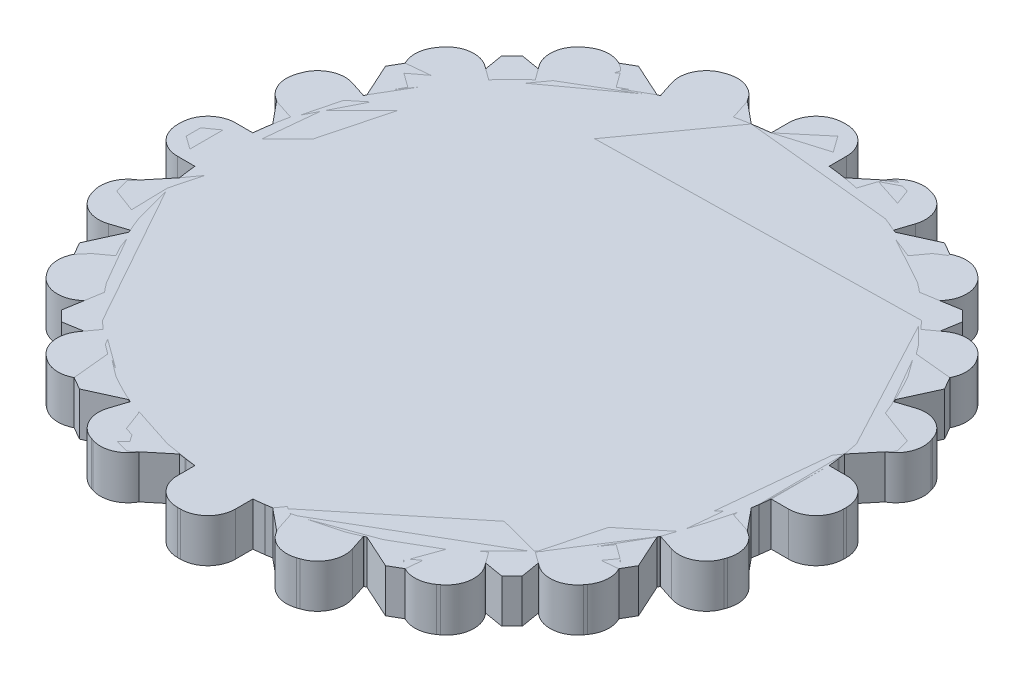
SolidWorks part; units mm, degrees
ref_plane "Front Plane" through (0, 0, 0) normal (0, 0, 1) x (1, 0, 0)
ref_plane "Top Plane" through (0, 0, 0) normal (0, 1, 0) x (1, 0, 0)
ref_plane "Right Plane" through (0, 0, 0) normal (1, 0, 0) x (0, 0, -1)
sketch "Sketch1" plane through (0, 0, 0) normal (0, 1, 0) x (1, 0, 0)
  line L86 (-3.1424, 4.8669) -> (1.8576, 4.8669)
  line L87 (-3.1424, 4.8669) -> (-3.1424, 1.8669)
  line L111 (-1.1424, 15.3669) -> (-0.1424, 15.3669)
  line L112 (-0.1424, 15.3669) -> (1.3576, 13.1649)
  line L113 (-1.1424, 15.3669) -> (-2.6424, 13.1649)
  line L114 (5.7906, 13.5092) -> (5.9886, 10.8522)
  line L115 (4.9246, 14.0092) -> (5.7906, 13.5092)
  line L116 (4.9246, 14.0092) -> (2.5245, 12.8522)
  line L117 (9.9999, 8.9339) -> (8.8429, 6.5338)
  line L118 (9.4999, 9.7999) -> (9.9999, 8.9339)
  line L119 (9.4999, 9.7999) -> (6.8429, 9.9979)
  line L120 (11.3576, 2.8669) -> (9.1556, 1.3669)
  line L121 (11.3576, 3.8669) -> (11.3576, 2.8669)
  line L122 (11.3576, 3.8669) -> (9.1556, 5.3669)
  line L123 (9.4999, -3.0661) -> (6.8429, -3.2641)
  line L124 (9.9999, -2.2001) -> (9.4999, -3.0661)
  line L125 (9.9999, -2.2001) -> (8.8429, 0.2)
  line L126 (4.9246, -7.2754) -> (2.5245, -6.1184)
  line L127 (5.7906, -6.7754) -> (4.9246, -7.2754)
  line L128 (5.7906, -6.7754) -> (5.9886, -4.1184)
  line L129 (-1.1424, -8.6331) -> (-2.6424, -6.4311)
  line L130 (-0.1424, -8.6331) -> (-1.1424, -8.6331)
  line L131 (-0.1424, -8.6331) -> (1.3576, -6.4311)
  line L132 (-7.0754, -6.7754) -> (-7.2734, -4.1184)
  line L133 (-6.2094, -7.2754) -> (-7.0754, -6.7754)
  line L134 (-6.2094, -7.2754) -> (-3.8093, -6.1184)
  line L135 (-11.2847, -2.2001) -> (-10.1277, 0.2)
  line L136 (-10.7847, -3.0661) -> (-11.2847, -2.2001)
  line L137 (-10.7847, -3.0661) -> (-8.1277, -3.2641)
  line L138 (-12.6424, 3.8669) -> (-10.4404, 5.3669)
  line L139 (-12.6424, 2.8669) -> (-12.6424, 3.8669)
  line L140 (-12.6424, 2.8669) -> (-10.4404, 1.3669)
  line L141 (-10.7847, 9.7999) -> (-8.1277, 9.9979)
  line L142 (-11.2847, 8.9339) -> (-10.7847, 9.7999)
  line L143 (-11.2847, 8.9339) -> (-10.1277, 6.5338)
  line L144 (-6.2094, 14.0092) -> (-3.8093, 12.8522)
  line L145 (-7.0754, 13.5092) -> (-6.2094, 14.0092)
  line L146 (-7.0754, 13.5092) -> (-7.2734, 10.8522)
  line L147 (-3.1424, 1.8669) -> (1.8576, 1.8669)
  line L148 (1.8576, 4.8669) -> (1.8576, 1.8669)
  line L149 (-3.1424, 4.8669) -> (1.8576, 1.8669) construction
  line L150 (-3.1424, 1.8669) -> (1.8576, 4.8669) construction
  arc A43 (-2.6424, 13.1649) -> (-3.8093, 12.8522) centre (-0.6424, 3.3669) ccw
  arc A44 (-7.2734, 10.8522) -> (-8.1277, 9.9979) centre (-0.6424, 3.3669) ccw
  arc A45 (-10.1277, 6.5338) -> (-10.4404, 5.3669) centre (-0.6424, 3.3669) ccw
  arc A46 (-10.4404, 1.3669) -> (-10.1277, 0.2) centre (-0.6424, 3.3669) ccw
  arc A47 (-8.1277, -3.2641) -> (-7.2734, -4.1184) centre (-0.6424, 3.3669) ccw
  arc A48 (-3.8093, -6.1184) -> (-2.6424, -6.4311) centre (-0.6424, 3.3669) ccw
  arc A49 (1.3576, -6.4311) -> (2.5245, -6.1184) centre (-0.6424, 3.3669) ccw
  arc A50 (5.9886, -4.1184) -> (6.8429, -3.2641) centre (-0.6424, 3.3669) ccw
  arc A51 (8.8429, 0.2) -> (9.1556, 1.3669) centre (-0.6424, 3.3669) ccw
  arc A52 (9.1556, 5.3669) -> (8.8429, 6.5338) centre (-0.6424, 3.3669) ccw
  arc A53 (6.8429, 9.9979) -> (5.9886, 10.8522) centre (-0.6424, 3.3669) ccw
  arc A54 (2.5245, 12.8522) -> (1.3576, 13.1649) centre (-0.6424, 3.3669) ccw
  point P6 (0, 0)
  point P8 (0, 0)
  point P9 (0, 0)
  point P12 (0, 2.7462)
  point P17 (0, 0)
  point P18 (0, 2.7462)
  point P22 (-2.5, 0.7462)
  point P63 (0, 0)
  point P68 (0, 0)
  point P69 (-0.6424, 3.3669)
  point P119 (0, 0)
  dimension "D1" = 20
  dimension "D2" = 3
  dimension "D3" = 5
  dimension "D8" = 12
sketch "Sketch2" plane through (0, 0, 0) normal (0, 1, 0) x (1, 0, 0)
  line L0 (-2, 0) -> (2, 0)
  line L1 (-23, -0.1) -> (-23, 0.1)
  line L2 (-21.1, 2) -> (-19.8997, 2)
  line L3 (-21.1, -2) -> (-19.8997, -2)
  line L4 (-20.6853, 4.6181) -> (-19.5438, 4.2472)
  line L5 (-19.4493, 8.4224) -> (-18.3078, 8.0515)
  line L6 (-21.9052, 7.0123) -> (-21.8434, 7.2025)
  line L7 (-18.2458, 10.7842) -> (-17.2748, 10.0787)
  line L8 (-15.8947, 14.0203) -> (-14.9237, 13.3148)
  line L9 (-18.6662, 13.4382) -> (-18.5486, 13.6)
  line L10 (-14.0203, 15.8947) -> (-13.3148, 14.9237)
  line L11 (-10.7842, 18.2458) -> (-10.0787, 17.2748)
  line L12 (-13.6, 18.5486) -> (-13.4382, 18.6662)
  line L13 (-8.4224, 19.4493) -> (-8.0515, 18.3078)
  line L14 (-4.6181, 20.6853) -> (-4.2472, 19.5438)
  line L15 (-7.2025, 21.8434) -> (-7.0123, 21.9052)
  line L16 (-2, 21.1) -> (-2, 19.8997)
  line L17 (2, 21.1) -> (2, 19.8997)
  line L18 (-0.1, 23) -> (0.1, 23)
  line L19 (4.6181, 20.6853) -> (4.2472, 19.5438)
  line L20 (8.4224, 19.4493) -> (8.0515, 18.3078)
  line L21 (7.0123, 21.9052) -> (7.2025, 21.8434)
  line L22 (10.7842, 18.2458) -> (10.0787, 17.2748)
  line L23 (14.0203, 15.8947) -> (13.3148, 14.9237)
  line L24 (13.4382, 18.6662) -> (13.6, 18.5486)
  line L25 (15.8947, 14.0203) -> (14.9237, 13.3148)
  line L26 (18.2458, 10.7842) -> (17.2748, 10.0787)
  line L27 (18.5486, 13.6) -> (18.6662, 13.4382)
  line L28 (19.4493, 8.4224) -> (18.3078, 8.0515)
  line L29 (20.6853, 4.6181) -> (19.5438, 4.2472)
  line L30 (21.8434, 7.2025) -> (21.9052, 7.0123)
  line L31 (21.1, 2) -> (19.8997, 2)
  line L32 (21.1, -2) -> (19.8997, -2)
  line L33 (23, 0.1) -> (23, -0.1)
  line L34 (20.6853, -4.6181) -> (19.5438, -4.2472)
  line L35 (19.4493, -8.4224) -> (18.3078, -8.0515)
  line L36 (21.9052, -7.0123) -> (21.8434, -7.2025)
  line L37 (18.2458, -10.7842) -> (17.2748, -10.0787)
  line L38 (15.8947, -14.0203) -> (14.9237, -13.3148)
  line L39 (18.6662, -13.4382) -> (18.5486, -13.6)
  line L40 (14.0203, -15.8947) -> (13.3148, -14.9237)
  line L41 (10.7842, -18.2458) -> (10.0787, -17.2748)
  line L42 (13.6, -18.5486) -> (13.4382, -18.6662)
  line L43 (8.4224, -19.4493) -> (8.0515, -18.3078)
  line L44 (4.6181, -20.6853) -> (4.2472, -19.5438)
  line L45 (7.2025, -21.8434) -> (7.0123, -21.9052)
  line L46 (2, -21.1) -> (2, -19.8997)
  line L47 (-2, -21.1) -> (-2, -19.8997)
  line L48 (0.1, -23) -> (-0.1, -23)
  line L49 (-4.6181, -20.6853) -> (-4.2472, -19.5438)
  line L50 (-8.4224, -19.4493) -> (-8.0515, -18.3078)
  line L51 (-7.0123, -21.9052) -> (-7.2025, -21.8434)
  line L52 (-10.7842, -18.2458) -> (-10.0787, -17.2748)
  line L53 (-14.0203, -15.8947) -> (-13.3148, -14.9237)
  line L54 (-13.4382, -18.6662) -> (-13.6, -18.5486)
  line L55 (-15.8947, -14.0203) -> (-14.9237, -13.3148)
  line L56 (-18.2458, -10.7842) -> (-17.2748, -10.0787)
  line L57 (-18.5486, -13.6) -> (-18.6662, -13.4382)
  line L58 (-19.4493, -8.4224) -> (-18.3078, -8.0515)
  line L59 (-20.6853, -4.6181) -> (-19.5438, -4.2472)
  line L60 (-21.8434, -7.2025) -> (-21.9052, -7.0123)
  arc A0 (-18.3078, -8.0515) -> (-17.2748, -10.0787) centre (0, 0) ccw
  arc A1 (-21.1, 2) -> (-23, 0.1) centre (-21.1, 0.1) ccw
  arc A2 (-21.1, -2) -> (-23, -0.1) centre (-21.1, -0.1) cw
  arc A3 (-20.6853, 4.6181) -> (-21.9052, 7.0123) centre (-20.0982, 6.4252) cw
  arc A4 (-19.4493, 8.4224) -> (-21.8434, 7.2025) centre (-20.0364, 6.6154) ccw
  arc A5 (-18.2458, 10.7842) -> (-18.6662, 13.4382) centre (-17.129, 12.3214) cw
  arc A6 (-15.8947, 14.0203) -> (-18.5486, 13.6) centre (-17.0115, 12.4832) ccw
  arc A7 (-14.0203, 15.8947) -> (-13.6, 18.5486) centre (-12.4832, 17.0115) cw
  arc A8 (-10.7842, 18.2458) -> (-13.4382, 18.6662) centre (-12.3214, 17.129) ccw
  arc A9 (-8.4224, 19.4493) -> (-7.2025, 21.8434) centre (-6.6154, 20.0364) cw
  arc A10 (-4.6181, 20.6853) -> (-7.0123, 21.9052) centre (-6.4252, 20.0982) ccw
  arc A11 (-2, 21.1) -> (-0.1, 23) centre (-0.1, 21.1) cw
  arc A12 (2, 21.1) -> (0.1, 23) centre (0.1, 21.1) ccw
  arc A13 (4.6181, 20.6853) -> (7.0123, 21.9052) centre (6.4252, 20.0982) cw
  arc A14 (8.4224, 19.4493) -> (7.2025, 21.8434) centre (6.6154, 20.0364) ccw
  arc A15 (10.7842, 18.2458) -> (13.4382, 18.6662) centre (12.3214, 17.129) cw
  arc A16 (14.0203, 15.8947) -> (13.6, 18.5486) centre (12.4832, 17.0115) ccw
  arc A17 (15.8947, 14.0203) -> (18.5486, 13.6) centre (17.0115, 12.4832) cw
  arc A18 (18.2458, 10.7842) -> (18.6662, 13.4382) centre (17.129, 12.3214) ccw
  arc A19 (19.4493, 8.4224) -> (21.8434, 7.2025) centre (20.0364, 6.6154) cw
  arc A20 (20.6853, 4.6181) -> (21.9052, 7.0123) centre (20.0982, 6.4252) ccw
  arc A21 (21.1, 2) -> (23, 0.1) centre (21.1, 0.1) cw
  arc A22 (21.1, -2) -> (23, -0.1) centre (21.1, -0.1) ccw
  arc A23 (20.6853, -4.6181) -> (21.9052, -7.0123) centre (20.0982, -6.4252) cw
  arc A24 (19.4493, -8.4224) -> (21.8434, -7.2025) centre (20.0364, -6.6154) ccw
  arc A25 (18.2458, -10.7842) -> (18.6662, -13.4382) centre (17.129, -12.3214) cw
  arc A26 (15.8947, -14.0203) -> (18.5486, -13.6) centre (17.0115, -12.4832) ccw
  arc A27 (14.0203, -15.8947) -> (13.6, -18.5486) centre (12.4832, -17.0115) cw
  arc A28 (10.7842, -18.2458) -> (13.4382, -18.6662) centre (12.3214, -17.129) ccw
  arc A29 (8.4224, -19.4493) -> (7.2025, -21.8434) centre (6.6154, -20.0364) cw
  arc A30 (4.6181, -20.6853) -> (7.0123, -21.9052) centre (6.4252, -20.0982) ccw
  arc A31 (2, -21.1) -> (0.1, -23) centre (0.1, -21.1) cw
  arc A32 (-2, -21.1) -> (-0.1, -23) centre (-0.1, -21.1) ccw
  arc A33 (-4.6181, -20.6853) -> (-7.0123, -21.9052) centre (-6.4252, -20.0982) cw
  arc A34 (-8.4224, -19.4493) -> (-7.2025, -21.8434) centre (-6.6154, -20.0364) ccw
  arc A35 (-10.7842, -18.2458) -> (-13.4382, -18.6662) centre (-12.3214, -17.129) cw
  arc A36 (-14.0203, -15.8947) -> (-13.6, -18.5486) centre (-12.4832, -17.0115) ccw
  arc A37 (-15.8947, -14.0203) -> (-18.5486, -13.6) centre (-17.0115, -12.4832) cw
  arc A38 (-18.2458, -10.7842) -> (-18.6662, -13.4382) centre (-17.129, -12.3214) ccw
  arc A39 (-19.4493, -8.4224) -> (-21.8434, -7.2025) centre (-20.0364, -6.6154) cw
  arc A40 (-20.6853, -4.6181) -> (-21.9052, -7.0123) centre (-20.0982, -6.4252) ccw
  arc A41 (-19.8997, -2) -> (-19.5438, -4.2472) centre (0, 0) ccw
  arc A42 (-19.5438, 4.2472) -> (-19.8997, 2) centre (0, 0) ccw
  arc A43 (-17.2748, 10.0787) -> (-18.3078, 8.0515) centre (0, 0) ccw
  arc A44 (-13.3148, 14.9237) -> (-14.9237, 13.3148) centre (0, 0) ccw
  arc A45 (-8.0515, 18.3078) -> (-10.0787, 17.2748) centre (0, 0) ccw
  arc A46 (-2, 19.8997) -> (-4.2472, 19.5438) centre (0, 0) ccw
  arc A47 (4.2472, 19.5438) -> (2, 19.8997) centre (0, 0) ccw
  arc A48 (10.0787, 17.2748) -> (8.0515, 18.3078) centre (0, 0) ccw
  arc A49 (14.9237, 13.3148) -> (13.3148, 14.9237) centre (0, 0) ccw
  arc A50 (18.3078, 8.0515) -> (17.2748, 10.0787) centre (0, 0) ccw
  arc A51 (19.8997, 2) -> (19.5438, 4.2472) centre (0, 0) ccw
  arc A52 (19.5438, -4.2472) -> (19.8997, -2) centre (0, 0) ccw
  arc A53 (17.2748, -10.0787) -> (18.3078, -8.0515) centre (0, 0) ccw
  arc A54 (13.3148, -14.9237) -> (14.9237, -13.3148) centre (0, 0) ccw
  arc A55 (8.0515, -18.3078) -> (10.0787, -17.2748) centre (0, 0) ccw
  arc A56 (2, -19.8997) -> (4.2472, -19.5438) centre (0, 0) ccw
  arc A57 (-10.0787, -17.2748) -> (-8.0515, -18.3078) centre (0, 0) ccw
  arc A58 (-4.2472, -19.5438) -> (-2, -19.8997) centre (0, 0) ccw
  arc A59 (-14.9237, -13.3148) -> (-13.3148, -14.9237) centre (0, 0) ccw
  point P6 (0, 0)
  point P10 (-23, 2)
  point P170 (0, 0)
  dimension "D1" = 40
  dimension "D4" = 1.9
  dimension "D5" = 20
extrude "Boss-Extrude3" add sketch "Sketch2" along normal blind 3 contours L55 A59 L53 A36 L54 A35 L52 A57 L50 A34 L51 A33 L49 A58 L47 A32 L48 A31 L46 A56 L44 A30 L45 A29 L43 A55 L41 A28 L42 A27 L40 A54 L38 A26 L39 A25 L37 A53 L35 A24 L36 A23 L34 A52 L32 A22 L33 A21 region at (-22.3495, 0, 0)
sketch "Sketch3" plane through (0, 0, 0) normal (0, 1, 0) x (1, 0, 0)
  line L0 (-22, 0) -> (22, 0)
  line L1 (22, -0.5) -> (22, 0.5)
  line L2 (22, 0.5) -> (19.8997, 2)
  line L3 (22, -0.5) -> (19.8997, -2)
  line L4 (21.3798, -5.2111) -> (19.7393, -3.2186)
  line L5 (21.121, -6.177) -> (21.3798, -5.2111)
  line L6 (21.121, -6.177) -> (18.704, -7.0823)
  line L7 (19.3026, -10.567) -> (18.2337, -8.2178)
  line L8 (18.8026, -11.433) -> (19.3026, -10.567)
  line L9 (18.8026, -11.433) -> (16.2337, -11.6819)
  line L10 (15.9099, -15.2028) -> (15.4855, -12.657)
  line L11 (15.2028, -15.9099) -> (15.9099, -15.2028)
  line L12 (15.2028, -15.9099) -> (12.657, -15.4855)
  line L13 (11.433, -18.8026) -> (11.6819, -16.2337)
  line L14 (10.567, -19.3026) -> (11.433, -18.8026)
  line L15 (10.567, -19.3026) -> (8.2178, -18.2337)
  line L16 (6.177, -21.121) -> (7.0823, -18.704)
  line L17 (5.2111, -21.3798) -> (6.177, -21.121)
  line L18 (5.2111, -21.3798) -> (3.2186, -19.7393)
  line L19 (0.5, -22) -> (2, -19.8997)
  line L20 (-0.5, -22) -> (0.5, -22)
  line L21 (-0.5, -22) -> (-2, -19.8997)
  line L22 (-5.2111, -21.3798) -> (-3.2186, -19.7393)
  line L23 (-6.177, -21.121) -> (-5.2111, -21.3798)
  line L24 (-6.177, -21.121) -> (-7.0823, -18.704)
  line L25 (-10.567, -19.3026) -> (-8.2178, -18.2337)
  line L26 (-11.433, -18.8026) -> (-10.567, -19.3026)
  line L27 (-11.433, -18.8026) -> (-11.6819, -16.2337)
  line L28 (-15.2028, -15.9099) -> (-12.657, -15.4855)
  line L29 (-15.9099, -15.2028) -> (-15.2028, -15.9099)
  line L30 (-15.9099, -15.2028) -> (-15.4855, -12.657)
  line L31 (-18.8026, -11.433) -> (-16.2337, -11.6819)
  line L32 (-19.3026, -10.567) -> (-18.8026, -11.433)
  line L33 (-19.3026, -10.567) -> (-18.2337, -8.2178)
  line L34 (-21.121, -6.177) -> (-18.704, -7.0823)
  line L35 (-21.3798, -5.2111) -> (-21.121, -6.177)
  line L36 (-21.3798, -5.2111) -> (-19.7393, -3.2186)
  line L37 (-22, -0.5) -> (-19.8997, -2)
  line L38 (-22, 0.5) -> (-22, -0.5)
  line L39 (-22, 0.5) -> (-19.8997, 2)
  line L40 (-21.3798, 5.2111) -> (-19.7393, 3.2186)
  line L41 (-21.121, 6.177) -> (-21.3798, 5.2111)
  line L42 (-21.121, 6.177) -> (-18.704, 7.0823)
  line L43 (-19.3026, 10.567) -> (-18.2337, 8.2178)
  line L44 (-18.8026, 11.433) -> (-19.3026, 10.567)
  line L45 (-18.8026, 11.433) -> (-16.2337, 11.6819)
  line L46 (-15.9099, 15.2028) -> (-15.4855, 12.657)
  line L47 (-15.2028, 15.9099) -> (-15.9099, 15.2028)
  line L48 (-15.2028, 15.9099) -> (-12.657, 15.4855)
  line L49 (-11.433, 18.8026) -> (-11.6819, 16.2337)
  line L50 (-10.567, 19.3026) -> (-11.433, 18.8026)
  line L51 (-10.567, 19.3026) -> (-8.2178, 18.2337)
  line L52 (-6.177, 21.121) -> (-7.0823, 18.704)
  line L53 (-5.2111, 21.3798) -> (-6.177, 21.121)
  line L54 (-5.2111, 21.3798) -> (-3.2186, 19.7393)
  line L55 (-0.5, 22) -> (-2, 19.8997)
  line L56 (0.5, 22) -> (-0.5, 22)
  line L57 (0.5, 22) -> (2, 19.8997)
  line L58 (5.2111, 21.3798) -> (3.2186, 19.7393)
  line L59 (6.177, 21.121) -> (5.2111, 21.3798)
  line L60 (6.177, 21.121) -> (7.0823, 18.704)
  line L61 (10.567, 19.3026) -> (8.2178, 18.2337)
  line L62 (11.433, 18.8026) -> (10.567, 19.3026)
  line L63 (11.433, 18.8026) -> (11.6819, 16.2337)
  line L64 (15.2028, 15.9099) -> (12.657, 15.4855)
  line L65 (15.9099, 15.2028) -> (15.2028, 15.9099)
  line L66 (15.9099, 15.2028) -> (15.4855, 12.657)
  line L67 (18.8026, 11.433) -> (16.2337, 11.6819)
  line L68 (19.3026, 10.567) -> (18.8026, 11.433)
  line L69 (19.3026, 10.567) -> (18.2337, 8.2178)
  line L70 (21.121, 6.177) -> (18.704, 7.0823)
  line L71 (21.3798, 5.2111) -> (21.121, 6.177)
  line L72 (21.3798, 5.2111) -> (19.7393, 3.2186)
  arc A0 (-8.2178, -18.2337) -> (-7.0823, -18.704) centre (0, 0) ccw
  arc A1 (-12.657, -15.4855) -> (-11.6819, -16.2337) centre (0, 0) ccw
  arc A2 (-16.2337, -11.6819) -> (-15.4855, -12.657) centre (0, 0) ccw
  arc A3 (-18.704, -7.0823) -> (-18.2337, -8.2178) centre (0, 0) ccw
  arc A4 (-19.8997, -2) -> (-19.7393, -3.2186) centre (0, 0) ccw
  arc A5 (-19.7393, 3.2186) -> (-19.8997, 2) centre (0, 0) ccw
  arc A6 (-18.2337, 8.2178) -> (-18.704, 7.0823) centre (0, 0) ccw
  arc A7 (-15.4855, 12.657) -> (-16.2337, 11.6819) centre (0, 0) ccw
  arc A8 (-11.6819, 16.2337) -> (-12.657, 15.4855) centre (0, 0) ccw
  arc A9 (-7.0823, 18.704) -> (-8.2178, 18.2337) centre (0, 0) ccw
  arc A10 (-2, 19.8997) -> (-3.2186, 19.7393) centre (0, 0) ccw
  arc A11 (3.2186, 19.7393) -> (2, 19.8997) centre (0, 0) ccw
  arc A12 (8.2178, 18.2337) -> (7.0823, 18.704) centre (0, 0) ccw
  arc A13 (12.657, 15.4855) -> (11.6819, 16.2337) centre (0, 0) ccw
  arc A14 (16.2337, 11.6819) -> (15.4855, 12.657) centre (0, 0) ccw
  arc A15 (18.704, 7.0823) -> (18.2337, 8.2178) centre (0, 0) ccw
  arc A16 (19.8997, 2) -> (19.7393, 3.2186) centre (0, 0) ccw
  arc A17 (19.7393, -3.2186) -> (19.8997, -2) centre (0, 0) ccw
  arc A18 (18.2337, -8.2178) -> (18.704, -7.0823) centre (0, 0) ccw
  arc A19 (-3.2186, -19.7393) -> (-2, -19.8997) centre (0, 0) ccw
  arc A20 (2, -19.8997) -> (3.2186, -19.7393) centre (0, 0) ccw
  arc A21 (7.0823, -18.704) -> (8.2178, -18.2337) centre (0, 0) ccw
  arc A22 (11.6819, -16.2337) -> (12.657, -15.4855) centre (0, 0) ccw
  arc A23 (15.4855, -12.657) -> (16.2337, -11.6819) centre (0, 0) ccw
  point P6 (0, 0)
  point P7 (0, -12.952)
  point P8 (-6.2727, 0)
  point P9 (11.4668, 0)
  point P10 (0, 0)
  point P108 (0, 0)
  dimension "D1" = 40
  dimension "D2" = 22
  dimension "D3" = 2
  dimension "D4" = 24
extrude "Boss-Extrude5" add sketch "Sketch3" along normal blind 3 separate body contours L2 A16 L72 L71 L70 A15 L69 L68 L67 A14 L66 L65 L64 A13 L63 L62 L61 A12 L60 L59 L58 A11 L57 L56 L55 A10 L54 L53 L52 A9 L51 L50 L49 A8 L48 L47 L46 A7 L45 L44 L43 A6 L42 L41 L40 A5 L39 L38 L0 L1 | L10 A23 L9 L8 L7 A18 L6 L5 L4 A17 L3 L1 L0 L38 L37 A4 L36 L35 L34 A3 L33 L32 L31 A2 L30 L29 L28 A1 L27 L26 L25 A0 L24 L23 L22 A19 L21 L20 L19 A20 L18 L17 L16 A21 L15 L14 L13 A22 L12 L11 region at (0, 0, -8.8989) region at (0, 0, 8.8989)
extrude "Boss-Extrude6" add sketch "Sketch1" along normal blind 3 separate body
